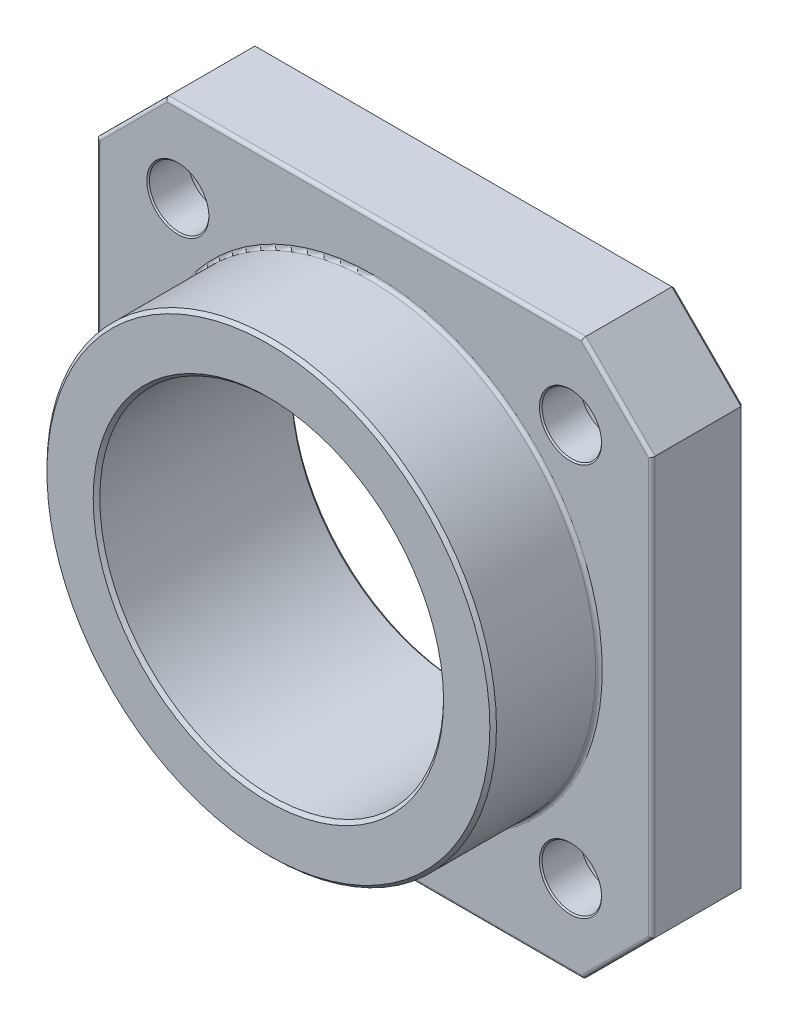
SolidWorks part; units mm, degrees
material "FE 370"
ref_plane "Piano frontale" through (0, 0, 0) normal (0, 0, 1) x (1, 0, 0)
ref_plane "Piano superiore" through (0, 0, 0) normal (0, 1, 0) x (1, 0, 0)
ref_plane "Piano destro" through (0, 0, 0) normal (1, 0, 0) x (0, 0, -1)
sketch "Schizzo1" plane through (0, 0, 0) normal (0, 0, 1) x (1, 0, 0)
  line L0 (-21, 15.7696) -> (-15.7696, 21)
  line L1 (-15.7696, -21) -> (15.7696, -21)
  line L2 (-21, -15.7696) -> (-21, 15.7696)
  line L3 (-15.7696, 21) -> (15.7696, 21)
  line L4 (21, -15.7696) -> (21, 15.7696)
  line L7 (36.7696, 0) -> (0, -36.7696) construction
  line L8 (36.7696, 0) -> (0, 36.7696) construction
  line L9 (0, 36.7696) -> (-36.7696, 0) construction
  line L10 (0, -36.7696) -> (-36.7696, 0) construction
  line L11 (36.7696, 0) -> (-36.7696, 0) construction
  line L12 (0, 36.7696) -> (0, -36.7696) construction
  line L13 (15.7696, 21) -> (21, 15.7696)
  line L14 (21, -15.7696) -> (15.7696, -21)
  line L15 (-21, -15.7696) -> (-15.7696, -21)
  circle A0 centre (0, 0) radius 13
  point P0 (0, 0)
  point P6 (0, 0)
  dimension "D5" = 26
  dimension "D1" = 42
  dimension "D2" = 42
  dimension "D3" = 52
  dimension "D4" = 52
  dimension "D6" = 42
extrude "Estrusione-Estrusione1" add sketch "Schizzo1" along normal blind 7
sketch "Schizzo2" plane through (0, 0, 7) normal (0, 0, 1) x (1, 0, 0)
  circle A0 centre (0, 0) radius 17
  circle A1 centre (0, 0) radius 13 construction
  circle A2 centre (0, 0) radius 13
  dimension "D1" = 34
extrude "Estrusione-Estrusione2" add sketch "Schizzo2" along normal blind 8
chamfer "Smusso1" distance 0.25 angle 45 9 edges at (13, 0, 0) (0, 21, 0) (-18.3848, 18.3848, 0) (-21, 0, 0) (-18.3848, -18.3848, 0) (0, -21, 0) (18.3848, -18.3848, 0) (21, 0, 0) (18.3848, 18.3848, 0)
chamfer "Smusso2" distance 0.25 angle 45 2 edges at (13, 0, 15) (17, 0, 15)
fillet "Raccordo1" radius 0.25 1 edges at (-17, 0, 7)
fillet "Raccordo2" radius 0.25 8 edges at (21, 0, 7) (18.3848, -18.3848, 7) (0, -21, 7) (-18.3848, -18.3848, 7) (-21, 0, 7) (-18.3848, 18.3848, 7) (0, 21, 7) (18.3848, 18.3848, 7)
sketch "Schizzo3" plane through (0, 0, 0) normal (0, 0, -1) x (-1, 0, 0)
  line L0 (-18.208, 18.208) -> (18.208, -18.208) construction
  line L1 (-15.666, 20.75) -> (-20.75, 15.666) construction
  line L2 (15.666, -20.75) -> (20.75, -15.666) construction
  line L3 (18.208, 18.208) -> (-18.208, -18.208) construction
  line L4 (20.75, 15.666) -> (15.666, 20.75) construction
  line L5 (-20.75, -15.666) -> (-15.666, -20.75) construction
  circle A0 centre (0, 0) radius 21 construction
  circle A1 centre (-14.8492, 14.8492) radius 2.25
  dimension "D1" = 42
  dimension "D2" = 4.5
extrude "Taglio-Estrusione1" cut sketch "Schizzo3" against normal through all
sketch "Schizzo4" plane through (0, 0, 0) normal (0, 0, -1) x (-1, 0, 0)
  circle A0 centre (-14.8492, 14.8492) radius 4
  dimension "D1" = 8
extrude "Taglio-Estrusione2" cut sketch "Schizzo4" against normal blind 4
ref_axis "Assi1" through (0, 0, 80.5857) along (0, 0, -1)
pattern_circular "RipetizioneCircolare1" count 4 over 360 about axis through (0, 0, 80.5857) along (0, 0, -1) of "Taglio-Estrusione1", "Taglio-Estrusione2"
chamfer "Smusso3" distance 0.1 angle 45 8 edges at (14.8492, -12.5992, 7) (-12.5992, -14.8492, 7) (-14.8492, 12.5992, 7) (12.5992, 14.8492, 7) (10.8492, 14.8492, 0) (-14.8492, 10.8492, 0) (-10.8492, -14.8492, 0) (14.8492, -10.8492, 0)
